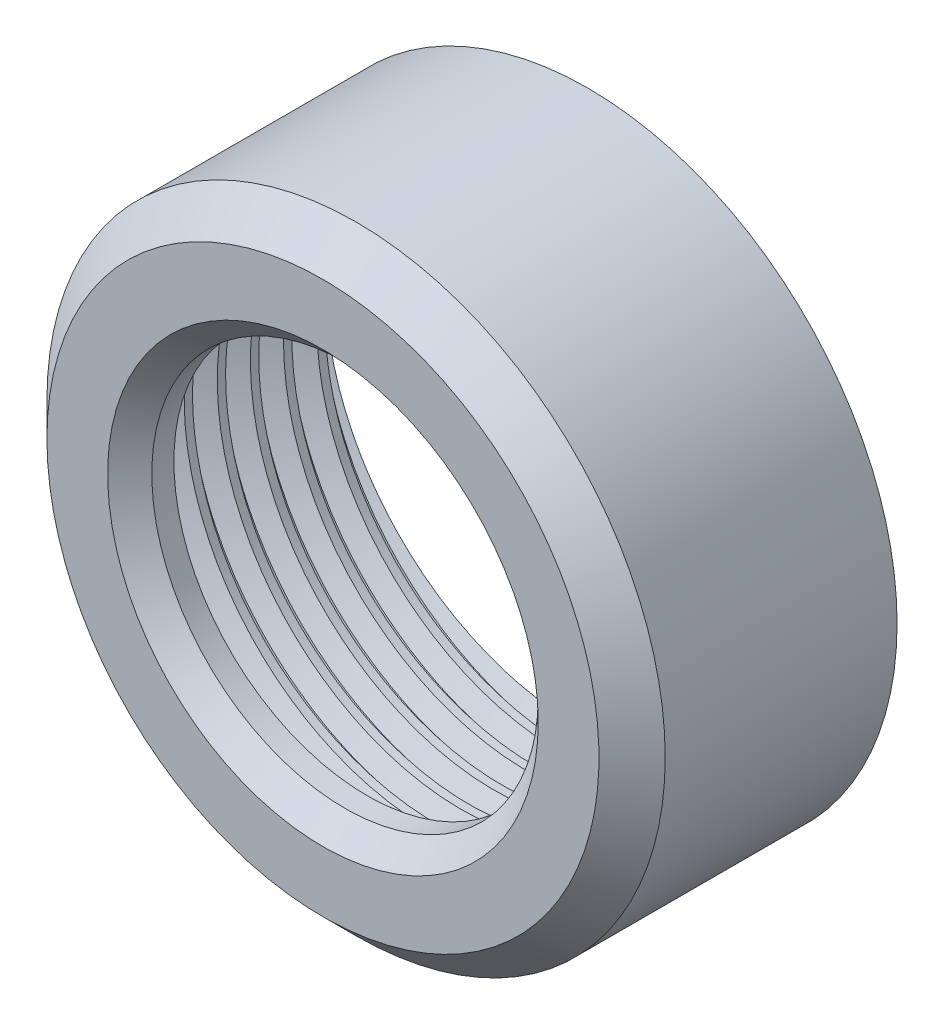
SolidWorks part; units mm, degrees
ref_plane "Front Plane" through (0, 0, 0) normal (0, 0, 1) x (1, 0, 0)
ref_plane "Top Plane" through (0, 0, 0) normal (0, 1, 0) x (1, 0, 0)
ref_plane "Right Plane" through (0, 0, 0) normal (1, 0, 0) x (0, 0, -1)
sketch "Sketch1" plane through (0, 0, 0) normal (0, 0, 1) x (1, 0, 0)
  circle A0 centre (0, 0) radius 8.75
  circle A1 centre (0, 0) radius 14
  dimension "D1" = 17.5
  dimension "D2" = 28
extrude "Boss-Extrude1" add sketch "Sketch1" along normal blind 2
sketch "Sketch2" plane through (0, 0, 0) normal (0, 0, -1) x (-1, 0, 0)
  circle A0 centre (0, 0) radius 12
  circle A1 centre (0, 0) radius 14 construction
  circle A2 centre (0, 0) radius 14
  dimension "D1" = 24
extrude "Boss-Extrude2" add sketch "Sketch2" along normal blind 10
chamfer "Chamfer1" distance 1 angle 45 1 edges at (8.75, 0, 2)
sketch "Sketch3" plane through (0, 0, 0) normal (0, 0, -1) x (-1, 0, 0)
  circle A0 centre (0, 0) radius 10.9
  circle A1 centre (0, 0) radius 9.5
  circle A2 centre (0, 0) radius 8.75 construction
  dimension "D1" = 1.4
  dimension "D2" = 0.75
extrude "Cut-Extrude1" cut sketch "Sketch3" against normal blind 0.7
thread "Thread2" pitch 1.5 method extrude trim with start face yes trim with end face yes profile "Thread Profile3" start angle 0, offset 2, length 0, pitch 1.5, diameter 24
ref_plane "Plane3" through (12, 0, -12) normal (0, -1, 0) x (1, 0, 0)
sketch "Thread Profile3" plane through (12, 0, -12) normal (0, -1, 0) x (1, 0, 0)
  line L0 (0, 0) -> (0, 1.5) construction
  line L11 (0, 0) -> (0, 1.3125)
  line L12 (0, 1.3125) -> (-0.8119, 0.8437)
  line L13 (-0.8119, 0.8437) -> (-0.8119, 0.4687)
  line L15 (-0.8119, 0.4687) -> (0, 0)
  line L17 (-0.8119, 0.6562) -> (0, 0.6562) construction
  point P2 (0, 0)
  dimension "Pitch" = 1.5
  dimension "Profile_Angle" = 60
  dimension "Profile_Land" = 0.375
  dimension "Profile_Height" = 0.8119
chamfer "Chamfer3" distance 1.5 angle 45 1 edges at (14, 0, 2)
